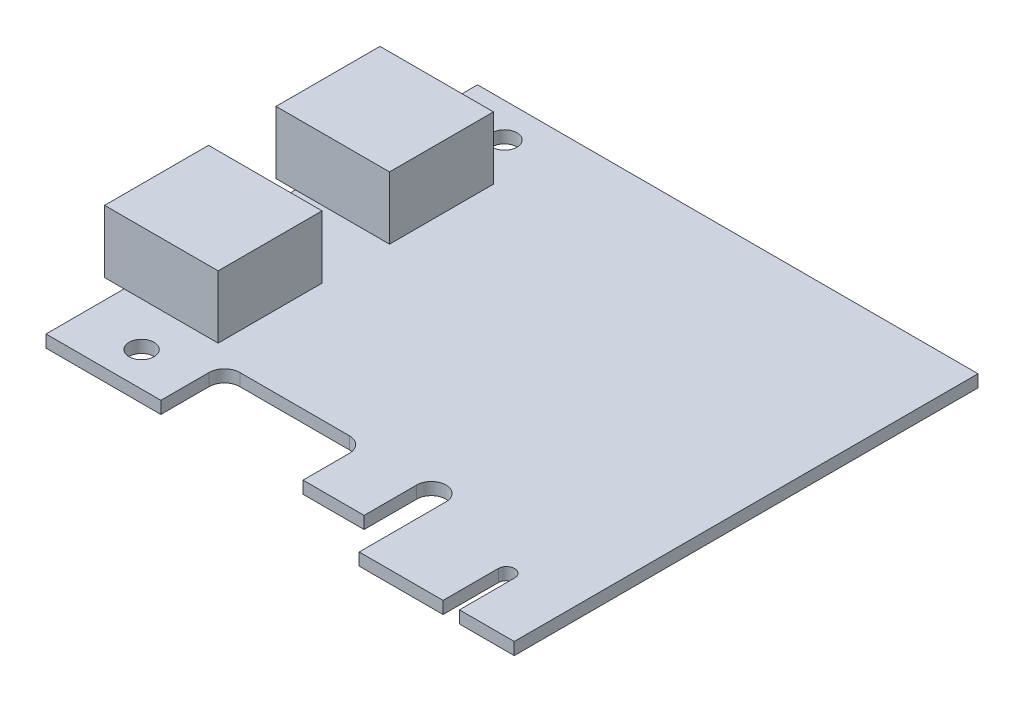
SolidWorks part; units mm, degrees
ref_plane "Front" through (0, 0, 0) normal (0, 0, 1) x (1, 0, 0)
ref_plane "Top" through (0, 0, 0) normal (0, 1, 0) x (1, 0, 0)
ref_plane "Right" through (0, 0, 0) normal (1, 0, 0) x (0, 0, -1)
sketch "Sketch1" plane through (0, 0, 0) normal (0, 1, 0) x (1, 0, 0)
  line L0 (23.3172, -30.2006) -> (23.3172, -23.0124)
  line L1 (12.3952, -30.2006) -> (23.3172, -30.2006)
  line L2 (-32.5882, -26.0096) -> (-32.5882, 30.2006)
  line L3 (-32.5882, 30.2006) -> (32.5882, 30.2006)
  line L4 (32.5882, -30.2006) -> (32.5882, 30.2006)
  line L5 (-32.5882, -30.2006) -> (32.5882, 30.2006) construction
  line L6 (-32.5882, 30.2006) -> (32.5882, -30.2006) construction
  line L7 (25.4508, -30.2006) -> (32.5882, -30.2006)
  line L8 (25.4508, -23.0124) -> (25.4508, -30.2006)
  line L9 (12.3952, -30.2006) -> (12.3952, -18.8976)
  line L10 (8.5852, -18.8976) -> (8.5852, -25.7556)
  line L11 (8.5852, -25.7556) -> (0.635, -25.7556)
  line L12 (0.635, -25.7556) -> (0.635, -19.7292)
  line L13 (-1.365, -17.7292) -> (-15.6276, -17.7292)
  line L14 (-17.6276, -19.7292) -> (-17.6276, -26.0096)
  line L15 (-17.6276, -26.0096) -> (-32.5882, -26.0096)
  line L16 (-32.5882, -26.0096) -> (-32.5882, -30.2006) construction
  line L17 (-32.5882, -30.2006) -> (12.3952, -30.2006) construction
  line L18 (23.3172, -30.2006) -> (25.4508, -30.2006) construction
  arc A0 (23.3172, -23.0124) -> (25.4508, -23.0124) centre (24.384, -23.0124) cw
  arc A1 (12.3952, -18.8976) -> (8.5852, -18.8976) centre (10.4902, -18.8976) ccw
  arc A2 (-1.365, -17.7292) -> (0.635, -19.7292) centre (-1.365, -19.7292) cw
  arc A3 (-15.6276, -17.7292) -> (-17.6276, -19.7292) centre (-15.6276, -19.7292) ccw
  point P0 (0, 0)
  point P15 (24.384, -21.9456)
  point P26 (10.4902, -16.9926)
  dimension "D3" = 2
  dimension "D14" = 14.9606
  dimension "D1" = 65.1764
  dimension "D2" = 60.4012
  dimension "D4" = 7.1374
  dimension "D5" = 2.1336
  dimension "D6" = 8.255
  dimension "D7" = 20.193
  dimension "D8" = 3.81
  dimension "D9" = 13.208
  dimension "D10" = 7.9502
  dimension "D11" = 4.445
  dimension "D12" = 56.2102
  dimension "D13" = 47.9298
extrude "Boss-Extrude1" add sketch "Sketch1" along normal blind 1.6
hole_wizard "#4 Clearance Hole1" positions "Sketch2" profile "Sketch3" hole size "#4" standard "ANSI Inch" end condition through all
sketch "Sketch2" plane through (0, 1.6, 0) normal (0, 1, 0) x (1, 0, 0)
  line L0 (-24.6126, 25.7302) -> (-24.6126, -21.5392)
  line L2 (-32.5882, 30.2006) -> (-32.5882, -26.0096) construction
  line L3 (-24.6126, 25.7302) -> (-24.6126, 30.2006)
  line L4 (32.5882, 30.2006) -> (-32.5882, 30.2006) construction
  line L6 (-24.6126, -21.5392) -> (-24.6126, -26.0096)
  line L7 (-32.5882, -26.0096) -> (-17.6276, -26.0096) construction
  point P0 (-24.6126, 25.7302)
  point P2 (-24.6126, -21.5392)
  dimension "D1" = 7.9756
  dimension "D2" = 47.2694
sketch "Sketch3" plane through (-24.6126, 1.6, -25.7302) normal (1, 0, 0) x (0, 0, 1)
  line L0 (0, 0) -> (0, 1.6)
  line L1 (0, 1.6) -> (1.6319, 1.6)
  line L2 (1.6319, 1.6) -> (1.6319, 0)
  line L5 (1.6319, 0) -> (0, 0)
  line L11 (0, -6.35) -> (0, 107.95) construction
  dimension "Thru Hole Dia." = 3.2639
  dimension "Thru Hole Depth" = 1.6
sketch "Sketch4" plane through (0, 1.6, 0) normal (0, 1, 0) x (1, 0, 0)
  line L0 (-32.5882, 30.2006) -> (-27.7368, 13.2588) construction
  line L1 (-35.1282, 6.4897) -> (-20.3454, 6.4897)
  line L2 (-35.1282, 6.4897) -> (-35.1282, 20.0279)
  line L3 (-35.1282, 20.0279) -> (-20.3454, 20.0279)
  line L4 (-20.3454, 6.4897) -> (-20.3454, 20.0279)
  line L5 (-35.1282, 6.4897) -> (-20.3454, 20.0279) construction
  line L6 (-35.1282, 20.0279) -> (-20.3454, 6.4897) construction
  line L7 (-35.1282, -15.8369) -> (-20.3454, -15.8369)
  line L8 (-35.1282, -15.8369) -> (-35.1282, -2.2987)
  line L9 (-35.1282, -2.2987) -> (-20.3454, -2.2987)
  line L10 (-20.3454, -15.8369) -> (-20.3454, -2.2987)
  line L11 (-35.1282, -15.8369) -> (-20.3454, -2.2987) construction
  line L12 (-35.1282, -2.2987) -> (-20.3454, -15.8369) construction
  line L13 (-27.7368, 13.2588) -> (-27.7368, -9.0678) construction
  line L14 (-27.7368, -9.0678) -> (-32.5882, -26.0096) construction
  line L15 (-32.5882, 30.2006) -> (-32.5882, -26.0096) construction
  point P0 (-27.7368, 13.2588)
  point P5 (-27.7368, -9.0678)
  dimension "D1" = 13.5382
  dimension "D2" = 14.7828
  dimension "D3" = 8.7884
  dimension "D4" = 2.54
extrude "Boss-Extrude2" add sketch "Sketch4" along normal blind 8.1534
